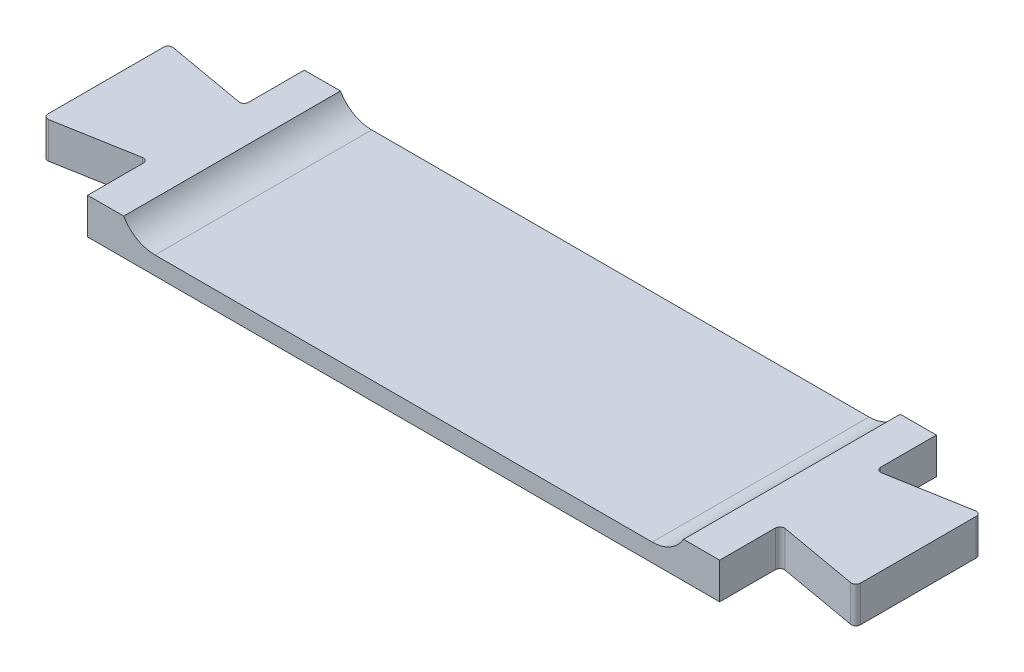
SolidWorks part; units mm, degrees
ref_plane "Front Plane" through (0, 0, 0) normal (0, 0, 1) x (1, 0, 0)
ref_plane "Top Plane" through (0, 0, 0) normal (0, 1, 0) x (1, 0, 0)
ref_plane "Right Plane" through (0, 0, 0) normal (1, 0, 0) x (0, 0, -1)
sketch "Sketch1" plane through (0, 0, 0) normal (0, 1, 0) x (1, 0, 0)
  line L0 (-17.5, 2.6184) -> (-22.5, 3.5)
  line L1 (-17.5, -6) -> (17.5, -6)
  line L2 (-17.5, -6) -> (-17.5, -2.6184)
  line L3 (-17.5, 6) -> (17.5, 6)
  line L4 (17.5, -6) -> (17.5, -2.6184)
  line L5 (-17.5, -6) -> (17.5, 6) construction
  line L6 (-17.5, 6) -> (17.5, -6) construction
  line L7 (-22.5, 3.5) -> (-22.5, -3.5)
  line L8 (-10, 0) -> (-18.3718, 0) construction
  line L9 (-17.5, -2.6184) -> (-22.5, -3.5)
  line L10 (-17.5, 2.6184) -> (-17.5, 6)
  line L11 (0, 0) -> (0, 6) construction
  line L12 (17.5, -2.6184) -> (22.5, -3.5)
  line L13 (22.5, 3.5) -> (22.5, -3.5)
  line L14 (17.5, 2.6184) -> (22.5, 3.5)
  line L15 (17.5, 2.6184) -> (17.5, 6)
  line L16 (-17.5, 6) -> (-27.9194, 6) construction
  point P0 (0, 0)
  point P13 (-22.5, 0)
  dimension "D1" = 12
  dimension "D2" = 35
  dimension "D3" = 3.5
  dimension "D4" = 80
  dimension "D5" = 5
extrude "Boss-Extrude1" add sketch "Sketch1" along normal blind 2
fillet "Fillet1" radius 0.25 8 edges at (-17.5, 1, 2.6184) (-22.5, 1, 3.5) (-22.5, 1, -3.5) (-17.5, 1, -2.6184) (17.5, 1, -2.6184) (22.5, 1, -3.5) (22.5, 1, 3.5) (17.5, 1, 2.6184)
shell "Shell1" [suppressed] thickness 1
fillet "Fillet2" [suppressed] radius 0.5
fillet "Fillet5" [suppressed] radius 1.5
sketch "Sketch2" plane through (0, 0, 0) normal (0, 0, 1) x (1, 0, 0)
  line L0 (-17.5, 2) -> (17.5, 2) construction
  line L1 (0, 0) -> (0, 2) construction
  line L2 (-14.5, 2) -> (-14.5, 5.1779)
  line L3 (-17.5, 0) -> (17.5, 0) construction
  line L4 (-14.5, 5.1779) -> (14.5, 5.1779)
  line L5 (14.5, 2) -> (14.5, 5.1779)
  spline S0 degree 3 poles (-14.5, 2) (-10.1117, 3.708) (-5.6899, 1.0248) (0, 1) knots 0 0 0 0 1 1 1 1
  spline S1 degree 3 poles (14.5, 2) (10.1117, 3.708) (5.6899, 1.0248) (0, 1) knots 0 0 0 0 1 1 1 1
  point P15 (0, 5.1779)
  dimension "D1" = 14.5
  dimension "D2" = 10
  dimension "D3" = 1
extrude "Cut-Extrude1" [suppressed] cut sketch "Sketch2" against normal mid plane 12
sketch "Sketch3" plane through (0, 2, 0) normal (0, 1, 0) x (1, 0, 0)
  line L0 (17.5, 6) -> (-17.5, 6) construction
  line L1 (-15.5, 6) -> (15.5, 6)
  line L2 (-15.5, 6) -> (-15.5, -6)
  line L3 (-15.5, -6) -> (15.5, -6)
  line L4 (15.5, 6) -> (15.5, -6)
  line L5 (-17.5, -6) -> (17.5, -6) construction
  line L6 (-17.5, 6) -> (-17.5, 2.9163) construction
  line L7 (17.5, 2.9163) -> (17.5, 6) construction
  point P8 (-17.5, 4.4582)
  point P11 (17.5, 4.4582)
  dimension "D1" = 2
  dimension "D2" = 2
extrude "Cut-Extrude2" cut sketch "Sketch3" against normal blind 1
fillet "Fillet6" radius 2 2 edges at (-15.5, 1, 0) (15.5, 1, 0)
